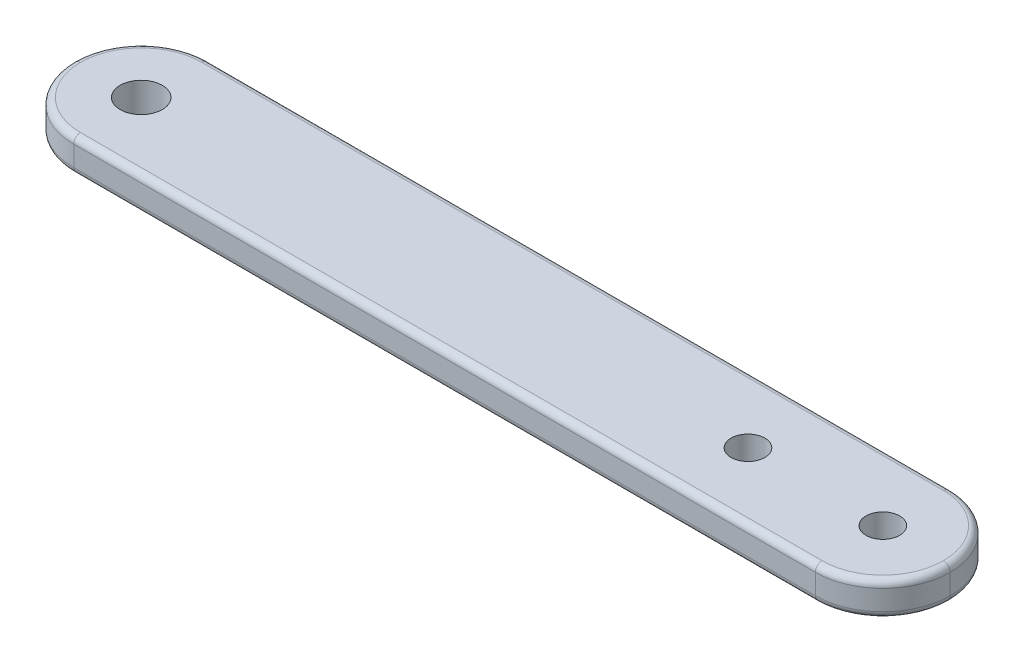
SolidWorks part; units mm, degrees
material "Plain Carbon Steel"
ref_plane "Front Plane" through (0, 0, 0) normal (0, 0, 1) x (1, 0, 0)
ref_plane "Top Plane" through (0, 0, 0) normal (0, 1, 0) x (1, 0, 0)
ref_plane "Right Plane" through (0, 0, 0) normal (1, 0, 0) x (0, 0, -1)
sketch "Sketch1" plane through (0, 0, 0) normal (0, 1, 0) x (1, 0, 0)
  line L0 (-82.55, 0) -> (82.55, 0) construction
  line L1 (82.55, -12.7) -> (-82.55, -12.7)
  line L2 (82.55, -12.7) -> (82.55, 12.7)
  line L3 (82.55, 12.7) -> (-82.55, 12.7)
  line L4 (-82.55, -12.7) -> (-82.55, 12.7)
  line L5 (82.55, -12.7) -> (-82.55, 12.7) construction
  line L6 (82.55, 12.7) -> (-82.55, -12.7) construction
  circle A0 centre (-69.85, 0) radius 3.9687
  circle A1 centre (44.45, 0) radius 3.175
  circle A2 centre (69.85, 0) radius 3.175
  point P0 (0, 0)
  dimension "D3" = 7.9375
  dimension "D4" = 6.35
  dimension "D1" = 25.4
  dimension "D2" = 12.7
  dimension "D5" = 12.7
  dimension "D6" = 114.3
  dimension "D7" = 25.4
extrude "Boss-Extrude1" add sketch "Sketch1" along normal blind 6.35
fillet "Fillet2" radius 12.7 4 edges at (-82.55, 3.175, 12.7) (-82.55, 3.175, -12.7) (82.55, 3.175, -12.7) (82.55, 3.175, 12.7)
fillet "Fillet1" radius 1.27 12 edges at (0, 0, -12.7) (0, 6.35, -12.7) (0, 0, 12.7) (0, 6.35, 12.7) (-78.8303, 0, -8.9803) (-78.8303, 6.35, -8.9803) (-78.8303, 0, 8.9803) (78.8303, 0, -8.9803) (78.8303, 0, 8.9803) (-78.8303, 6.35, 8.9803) (78.8303, 6.35, -8.9803) (78.8303, 6.35, 8.9803)
